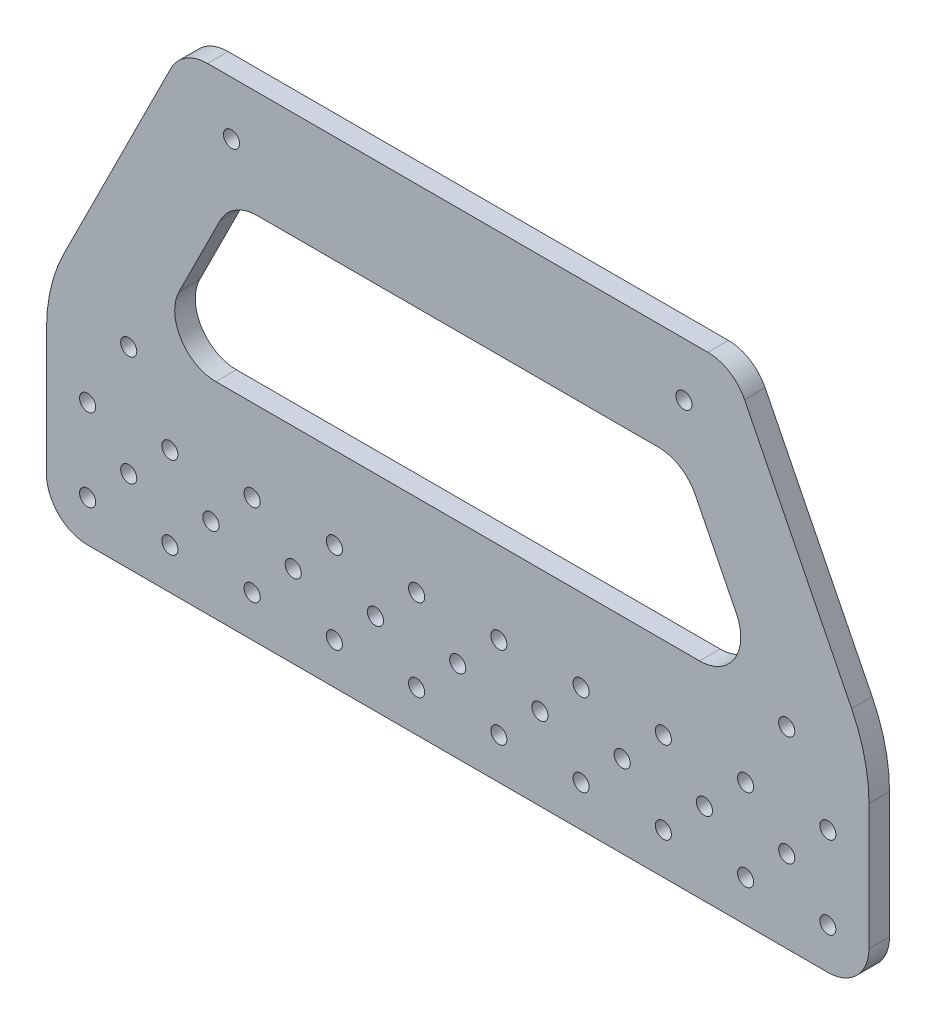
SolidWorks part; units mm, degrees
material "PC High Viscosity"
ref_plane "Front Plane" through (0, 0, 0) normal (0, 0, 1) x (1, 0, 0)
ref_plane "Top Plane" through (0, 0, 0) normal (0, 1, 0) x (1, 0, 0)
ref_plane "Right Plane" through (0, 0, 0) normal (1, 0, 0) x (0, 0, -1)
sketch "Sketch1" plane through (0, 0, 0) normal (0, 0, 1) x (1, 0, 0)
  line L0 (40.9398, 81.8796) -> (53.6398, 107.2796)
  line L1 (12.7, 0) -> (241.3, 0)
  line L2 (0, 12.7) -> (0, 51.5077)
  line L3 (52.299, 63.5) -> (201.701, 63.5)
  line L4 (254, 12.7) -> (254, 51.5077)
  line L5 (57.15, 63.5) -> (196.85, 63.5)
  line L6 (57.15, 63.5) -> (57.15, 114.3) construction
  line L7 (64.999, 114.3) -> (189.001, 114.3)
  line L8 (196.85, 63.5) -> (196.85, 114.3) construction
  line L9 (213.0602, 81.8796) -> (200.3602, 107.2796)
  line L10 (5.3631, 74.2262) -> (38.3998, 140.2996)
  line L11 (49.759, 147.32) -> (204.241, 147.32)
  line L12 (215.6002, 140.2996) -> (248.6369, 74.2262)
  line L13 (0, 63.5) -> (31.75, 63.5) construction
  line L14 (222.25, 63.5) -> (254, 63.5) construction
  arc A0 (204.241, 147.32) -> (215.6002, 140.2996) centre (204.241, 134.62) cw
  arc A1 (38.3998, 140.2996) -> (49.759, 147.32) centre (49.759, 134.62) cw
  arc A2 (189.001, 114.3) -> (200.3602, 107.2796) centre (189.001, 101.6) cw
  arc A3 (213.0602, 81.8796) -> (201.701, 63.5) centre (201.701, 76.2) cw
  arc A4 (40.9398, 81.8796) -> (52.299, 63.5) centre (52.299, 76.2) ccw
  arc A5 (53.6398, 107.2796) -> (64.999, 114.3) centre (64.999, 101.6) cw
  arc A6 (248.6369, 74.2262) -> (254, 51.5077) centre (203.2, 51.5077) cw
  arc A7 (0, 51.5077) -> (5.3631, 74.2262) centre (50.8, 51.5077) cw
  arc A8 (241.3, 0) -> (254, 12.7) centre (241.3, 12.7) ccw
  arc A9 (12.7, 0) -> (0, 12.7) centre (12.7, 12.7) cw
  point P40 (254, 0)
  point P43 (0, 0)
  dimension "D9" = 12.7
  dimension "D10" = 50.8
  dimension "D11" = 12.7
  dimension "D1" = 63.5
  dimension "D2" = 254
  dimension "D3" = 50.8
  dimension "D4" = 139.7
  dimension "D5" = 57.15
  dimension "D6" = 25.4
  dimension "D7" = 25.4
  dimension "D8" = 33.02
extrude "Boss-Extrude1" add sketch "Sketch1" along normal blind 6.35 contours A1 L10 L2 L1 L4 L12 A0 L11 L0 A5 L7 A2 L9 A3 L3 A4 region at (127, 62.9596, 0)
sketch "Sketch2" plane through (0, 0, 6.35) normal (0, 0, 1) x (1, 0, 0)
  line L0 (12.7, 0) -> (241.3, 0) construction
  line L1 (254, 12.7) -> (254, 51.5077) construction
  line L2 (241.3, 12.7) -> (215.9, 12.7) construction
  line L3 (241.3, 12.7) -> (241.3, 38.1) construction
  line L4 (25.4, 25.4) -> (50.8, 25.4) construction
  circle A0 centre (241.3, 12.7) radius 2.4892
  circle A1 centre (215.9, 12.7) radius 2.4892
  circle A2 centre (190.5, 12.7) radius 2.4892
  circle A3 centre (165.1, 12.7) radius 2.4892
  circle A4 centre (139.7, 12.7) radius 2.4892
  circle A5 centre (114.3, 12.7) radius 2.4892
  circle A6 centre (88.9, 12.7) radius 2.4892
  circle A7 centre (63.5, 12.7) radius 2.4892
  circle A8 centre (38.1, 12.7) radius 2.4892
  circle A9 centre (12.7, 12.7) radius 2.4892
  circle A10 centre (215.9, 38.1) radius 2.4892
  circle A11 centre (190.5, 38.1) radius 2.4892
  circle A12 centre (165.1, 38.1) radius 2.4892
  circle A13 centre (139.7, 38.1) radius 2.4892
  circle A14 centre (114.3, 38.1) radius 2.4892
  circle A15 centre (88.9, 38.1) radius 2.4892
  circle A16 centre (63.5, 38.1) radius 2.4892
  circle A17 centre (38.1, 38.1) radius 2.4892
  circle A18 centre (12.7, 38.1) radius 2.4892
  circle A19 centre (241.3, 38.1) radius 2.4892
  circle A20 centre (25.4, 25.4) radius 2.4892
  circle A21 centre (50.8, 25.4) radius 2.4892
  circle A22 centre (76.2, 25.4) radius 2.4892
  circle A23 centre (101.6, 25.4) radius 2.4892
  circle A24 centre (127, 25.4) radius 2.4892
  circle A25 centre (152.4, 25.4) radius 2.4892
  circle A26 centre (177.8, 25.4) radius 2.4892
  circle A27 centre (203.2, 25.4) radius 2.4892
  circle A28 centre (228.6, 25.4) radius 2.4892
  dimension "D1" = 4.9784
  dimension "D2" = 12.7
  dimension "D3" = 12.7
  dimension "D8" = 12.7
  dimension "D9" = 12.7
  dimension "D6" = 25.4
  dimension "D7" = 25.4
  dimension "D11" = 25.4
  dimension "D4" = 10
  dimension "D5" = 2
  dimension "D10" = 9
extrude "Cut-Extrude1" cut sketch "Sketch2" against normal through all
sketch "Sketch3" plane through (0, 0, 6.35) normal (0, 0, 1) x (1, 0, 0)
  line L0 (127, 0) -> (127, 147.32) construction
  line L1 (12.7, 0) -> (241.3, 0) construction
  line L2 (49.759, 147.32) -> (204.241, 147.32) construction
  line L3 (201.701, 76.2) -> (228.6, 59.3327) construction
  circle A0 centre (25.4, 59.3327) radius 2.4892
  circle A1 centre (57.15, 130.81) radius 2.4892
  circle A2 centre (196.85, 130.81) radius 2.4892
  circle A3 centre (228.6, 59.3327) radius 2.4892
  circle A4 centre (127, 130.81) radius 2.4892 construction
  arc A5 (201.701, 63.5) -> (213.0602, 81.8796) centre (201.701, 76.2) ccw construction
  arc A6 (201.701, 63.5) -> (213.0602, 81.8796) centre (201.701, 76.2) ccw
  dimension "D3" = 4.9784
  dimension "D4" = 101.6
  dimension "D5" = 101.6
  dimension "D7" = 16.51
  dimension "D1" = 69.85
  dimension "D2" = 69.85
  dimension "D6" = 31.75
extrude "Cut-Extrude2" cut sketch "Sketch3" against normal through all contours A1 | A4 | A2 | A3 | A0 region at (25.4, 59.3327, 6.35) region at (57.15, 130.81, 6.35) region at (196.85, 130.81, 6.35) region at (228.6, 59.3327, 6.35)
sketch "Sketch4" plane through (0, 0, 6.35) normal (0, 0, 1) x (1, 0, 0)
  line L0 (0, -1000) -> (0, 49000) construction
  line L1 (-1000, 0) -> (49000, 0) construction
  point P4 (0, 0)
  point P6 (0, 0)
